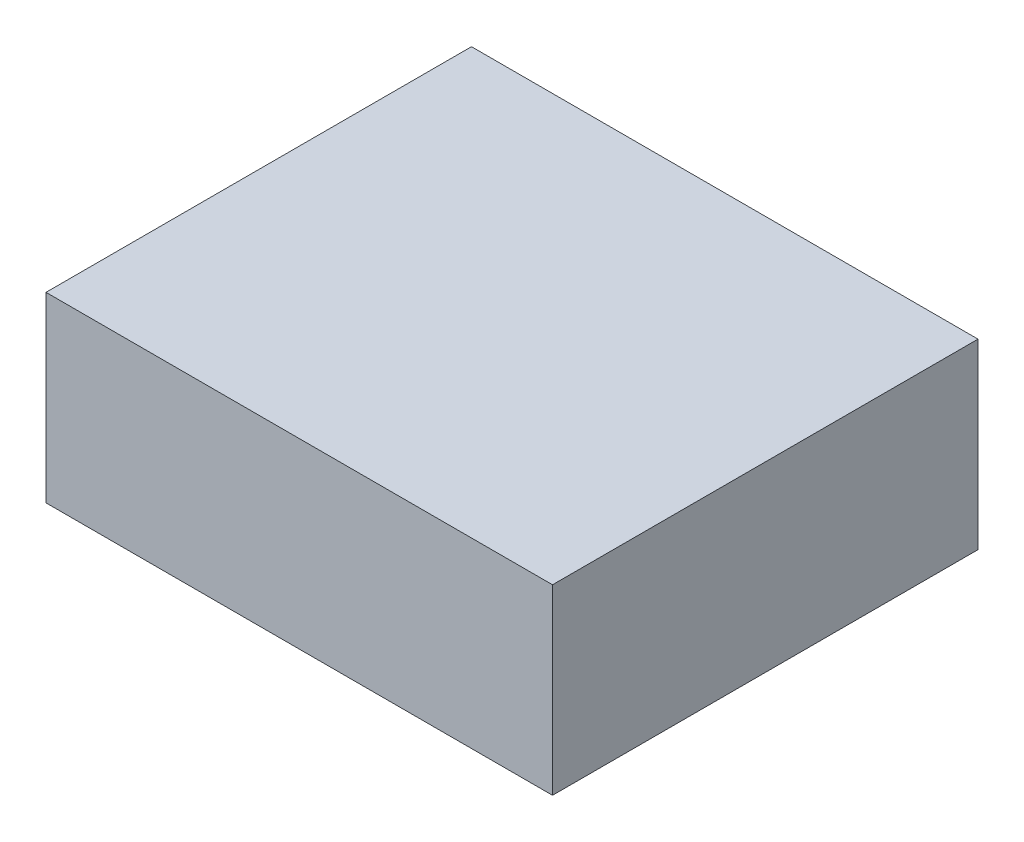
SolidWorks part; units mm, degrees
ref_plane "Front Plane" through (0, 0, 0) normal (0, 0, 1) x (1, 0, 0)
ref_plane "Top Plane" through (0, 0, 0) normal (0, 1, 0) x (1, 0, 0)
ref_plane "Right Plane" through (0, 0, 0) normal (1, 0, 0) x (0, 0, -1)
sketch "Sketch2" plane through (0, 0, 0) normal (0, 1, 0) x (1, 0, 0)
  line L1 (-12.5, 10.5) -> (12.5, 10.5)
  line L2 (-12.5, 10.5) -> (-12.5, -10.5)
  line L3 (-12.5, -10.5) -> (12.5, -10.5)
  line L4 (12.5, 10.5) -> (12.5, -10.5)
  line L5 (-12.5, 10.5) -> (12.5, -10.5) construction
  line L6 (-12.5, -10.5) -> (12.5, 10.5) construction
  point P0 (0, 0)
  dimension "D1" = 25
  dimension "D2" = 21
extrude "Boss-Extrude1" add sketch "Sketch2" along normal blind 4.5 and the other way blind 4.5
